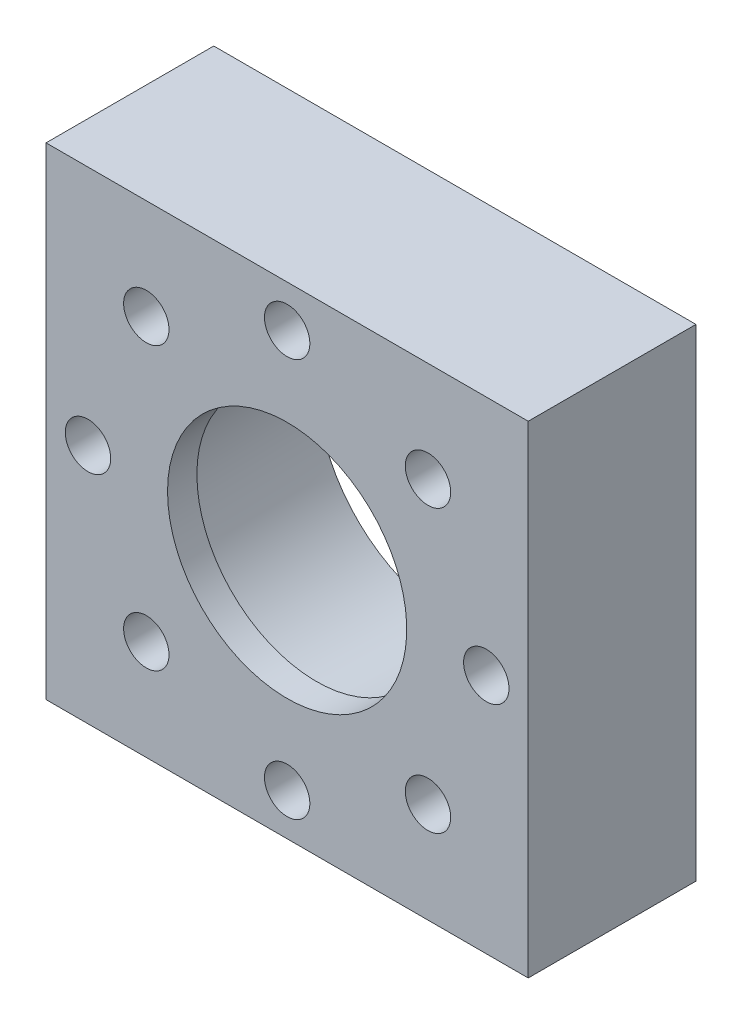
SolidWorks part; units mm, degrees
ref_plane "Front Plane" through (0, 0, 0) normal (0, 0, 1) x (1, 0, 0)
ref_plane "Top Plane" through (0, 0, 0) normal (0, 1, 0) x (1, 0, 0)
ref_plane "Right Plane" through (0, 0, 0) normal (1, 0, 0) x (0, 0, -1)
sketch "Sketch1" plane through (0, 0, 0) normal (0, 0, 1) x (1, 0, 0)
  line L0 (0, 0) -> (29.21, 0) construction
  line L1 (-29.21, -29.21) -> (29.21, -29.21)
  line L2 (-29.21, -29.21) -> (-29.21, 29.21)
  line L3 (-29.21, 29.21) -> (29.21, 29.21)
  line L4 (29.21, -29.21) -> (29.21, 29.21)
  line L5 (0, 0) -> (0, 29.21) construction
  dimension "D1" = 58.42
extrude "Boss-Extrude1" add sketch "Sketch1" along normal blind 20.32
sketch "Sketch5" plane through (0, 0, 0) normal (0, 0, -1) x (-1, 0, 0)
  point P0 (0, 0)
sketch "Sketch6" plane through (0, 0, 0) normal (0, 0, -1) x (-1, 0, 0)
  circle A0 centre (0, 0) radius 29.21 construction
  circle A1 centre (0, 0) radius 24.13 construction
  point P5 (0, 24.13)
  dimension "D1" = 58.42
  dimension "D2" = 5.08
hole_wizard "1 NPT Tapped Hole2" positions "Sketch5" profile "Sketch7" size "1" standard "ANSI Inch" end condition up to next
sketch "Sketch7" plane through (0, 0, 0) normal (1, 0, 0) x (0, 1, 0)
  line L0 (0, 0) -> (0, 20.32)
  line L1 (0, 20.32) -> (14.4907, 20.32)
  line L2 (-16.1979, 16.764) -> (-16.6998, 0) construction
  line L3 (14.4907, 20.32) -> (14.4907, 16.764)
  line L4 (14.4907, 16.764) -> (16.1979, 16.764)
  line L5 (16.1979, 16.764) -> (16.6998, 0)
  line L7 (16.6998, 0) -> (0, 0)
  line L8 (0, -6.35) -> (0, 107.95) construction
  line L11 (-14.4907, 16.764) -> (-16.1979, 16.764) construction
  dimension "Thru Tap Drill Dia." = 28.9814
  dimension "Thru Tap Drill Depth" = 20.32
  dimension "Thread Dia." = 33.3996
  dimension "Thread Angle" = 3.43
  dimension "Thread Depth" = 16.764
hole_wizard "M5 Clearance Hole1" positions "Sketch6" profile "Sketch8" hole size "M5" standard "ANSI Metric" end condition up to next
sketch "Sketch8" plane through (0, 24.13, 0) normal (1, 0, 0) x (0, 1, 0)
  line L0 (0, 0) -> (0, 20.32)
  line L1 (0, 20.32) -> (2.75, 20.32)
  line L2 (2.75, 20.32) -> (2.75, 0)
  line L5 (2.75, 0) -> (0, 0)
  line L11 (0, -6.35) -> (0, 107.95) construction
  dimension "Thru Hole Dia." = 5.5
  dimension "Thru Hole Depth" = 20.32
pattern_circular "CirPattern1" count 8 every 45 about axis through (0, 0, 0) along (0, 0, -1) of "M5 Clearance Hole1"
equation "\"le\"=2.43593"
equation "\"Cavity_Depth\" = 0.031in"
equation "\"Cavity_Width\" = 0.031in"
equation "\"Tooth_Width\" = .01in"
equation "\"Shaft_Seal_OD\"= 17mm'diameter at seal area"
equation "\"Shaft_clearance\"= .002in"
equation "\"O-Ring_ID\"= .801in"
equation "\"O-Ring_CS\"= .070in"
equation "\"Shaft_OD\"= .5in"
equation "\"Flange_OD\"=2.3in"
equation "\"D1@Sketch1\"=\"Flange_OD\""
equation "\"fitting_OD\" = 1.3in"
equation "\"plate_thick\"= .8in"
equation "\"D1@Boss-Extrude1\"=\"plate_thick\""
equation "\"D1@Sketch6\"=\"Flange_OD\""
